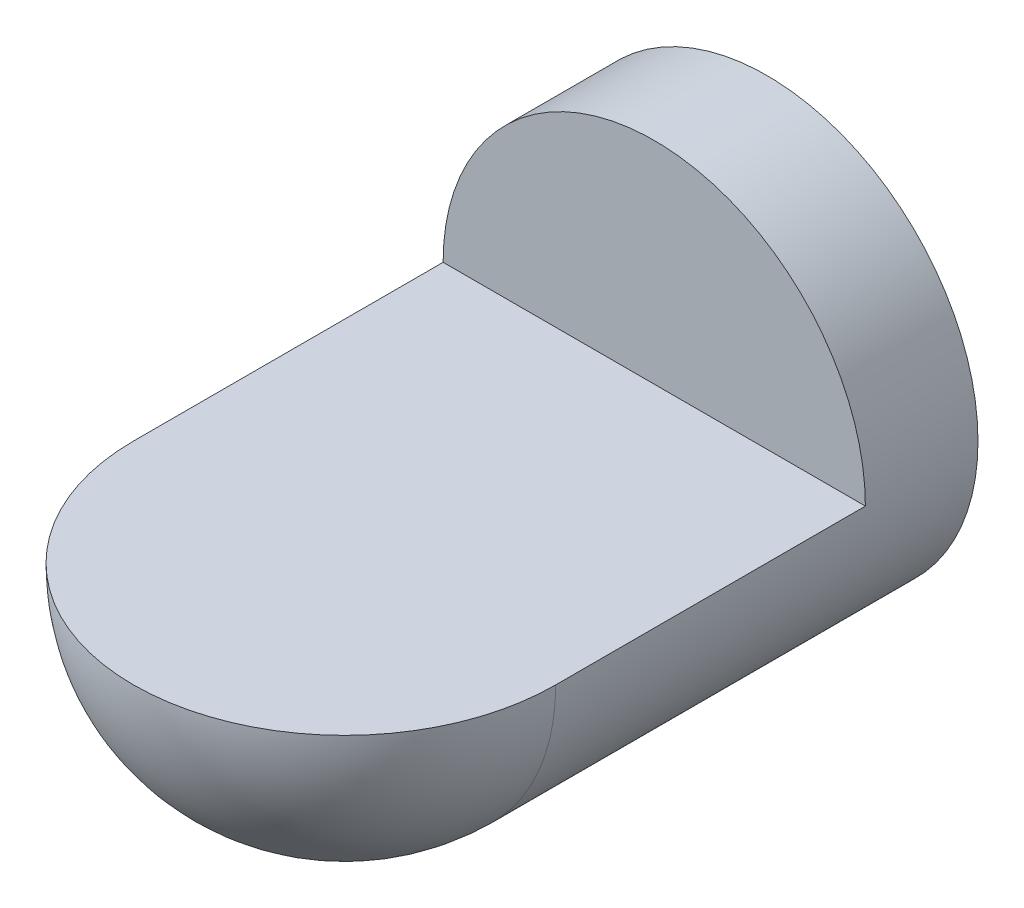
SolidWorks part; units mm, degrees
ref_plane "Front Plane" through (0, 0, 0) normal (0, 0, 1) x (1, 0, 0)
ref_plane "Top Plane" through (0, 0, 0) normal (0, 1, 0) x (1, 0, 0)
ref_plane "Right Plane" through (0, 0, 0) normal (1, 0, 0) x (0, 0, -1)
sketch "Sketch1" plane through (0, 0, 0) normal (1, 0, 0) x (0, 0, -1)
  line L0 (-146.9091, 0) -> (313.5945, 0) construction
  line L1 (150, 0) -> (-75, 0)
  line L2 (150, 0) -> (150, 75)
  line L3 (0, 75) -> (150, 75)
  arc A0 (-75, 0) -> (0, 75) centre (0, 0) cw
  dimension "D1" = 75
  dimension "D2" = 150
revolve "Revolve1" add sketch "Sketch1" angle 360 about L0
sketch "Sketch2" plane through (0, 0, 0) normal (1, 0, 0) x (0, 0, -1)
  line L0 (-88.0407, 0) -> (120.4455, 0) construction
  line L1 (110, 0) -> (110, 75)
  line L2 (150, 75) -> (0, 75) construction
  line L3 (110, 0) -> (-75, 0)
  line L4 (110, 75) -> (0, 75)
  line L5 (150, -75) -> (150, 75) construction
  arc A0 (0, 75) -> (0, -75) centre (0, 0) ccw construction
  arc A1 (-75, 0) -> (0, 75) centre (0, 0) cw
  dimension "D1" = 40
extrude "Cut-Extrude1" cut sketch "Sketch2" along normal through all and the other way through all
ref_axis "Axis1" through (0, 82.5, 0) along (0, -1, 0)
equation "\"base_link_length\"=150"
equation "\"link1_diameter\"=150"
equation "\"D1@Sketch1\"=\"link1_diameter\"/2"
equation "\"link1_length\"=150"
equation "\"D2@Sketch1\"=\"link1_length\""
equation "\"link2_diameter\"=150"
equation "\"link2_length\"=300"
equation "\"link3_diameter\"=150"
equation "\"link3_length\"=150"
equation "\"link4_diameter\"=150"
equation "\"link4_length\"=150"
equation "\"link5_diameter\"=150"
equation "\"link5_length\"=200"
equation "\"end_effector_diameter\"=150"
equation "\"end_effector_length\"=150"
equation "\"base_link_diameterA\"=200"
equation "\"base_link_diameterB\"=150"
equation "\"base_link_lengthA\"=50"
